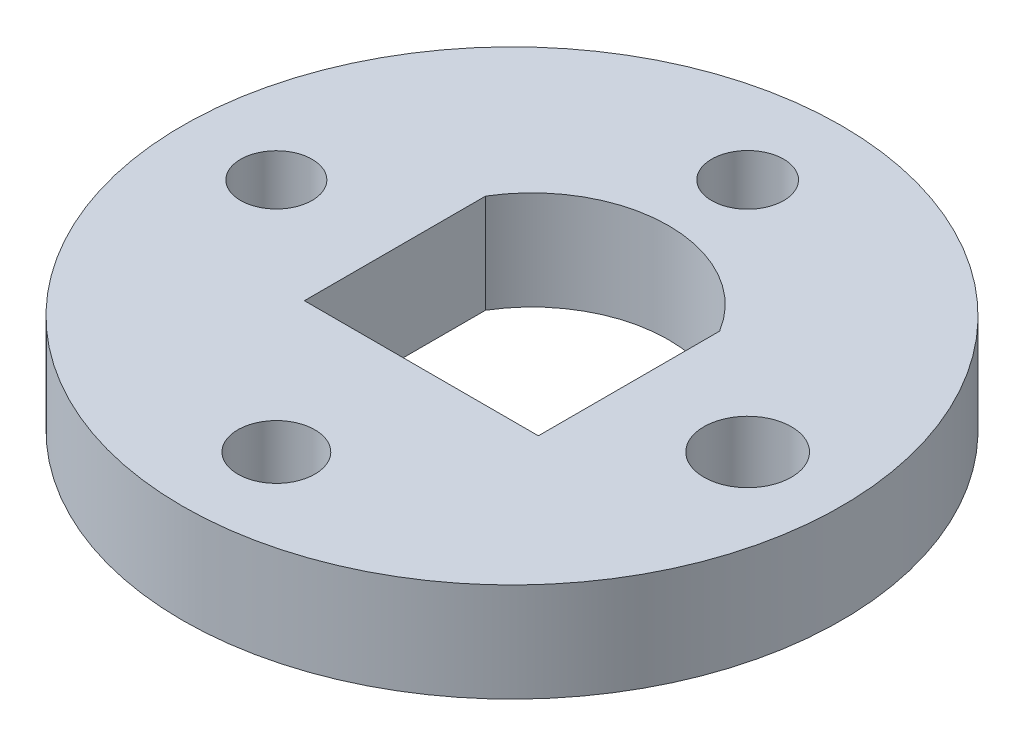
SolidWorks part; units mm, degrees
ref_plane "Front Plane" through (0, 0, 0) normal (0, 0, 1) x (1, 0, 0)
ref_plane "Top Plane" through (0, 0, 0) normal (0, 1, 0) x (1, 0, 0)
ref_plane "Right Plane" through (0, 0, 0) normal (1, 0, 0) x (0, 0, -1)
sketch "Sketch1" plane through (0, 0, 0) normal (0, 1, 0) x (1, 0, 0)
  circle A0 centre (0, 0) radius 25.4
  dimension "D1" = 50.8
extrude "Boss-Extrude1" add sketch "Sketch1" along normal blind 7.62
sketch "Sketch2" plane through (0, 7.62, 0) normal (0, 1, 0) x (1, 0, 0)
  line L1 (-9.017, -6.985) -> (9.017, -6.985)
  line L2 (-9.017, -6.985) -> (-9.017, 6.985)
  line L4 (9.017, -6.985) -> (9.017, 6.985)
  line L5 (-9.017, -6.985) -> (9.017, 6.985) construction
  line L6 (-9.017, 6.985) -> (9.017, -6.985) construction
  arc A0 (-9.017, 6.985) -> (9.017, 6.985) centre (0, 1.5224) cw
  point P0 (0, 0)
  point P7 (0, 12.065)
  dimension "D1" = 19.05
  dimension "D2" = 13.97
  dimension "D3" = 18.034
extrude "Cut-Extrude1" cut sketch "Sketch2" along direction (0, 1, 0) on the side against the normal through all
sketch "Sketch3" plane through (0, 7.62, 0) normal (0, 1, 0) x (1, 0, 0)
  circle A0 centre (-18.1622, 0) radius 2.7543
  circle A1 centre (0, 18.1622) radius 2.7743
  circle A2 centre (18.1622, 0) radius 3.3745
  circle A3 centre (0, -18.1622) radius 2.9677
  circle A4 centre (0, 0) radius 18.1622 construction
  point P11 (0, 0)
  point P12 (0, 0)
  point P13 (0, 0)
  point P14 (0, 0)
extrude "Cut-Extrude2" cut sketch "Sketch3" along direction (0, 1, 0) on the side against the normal through all
